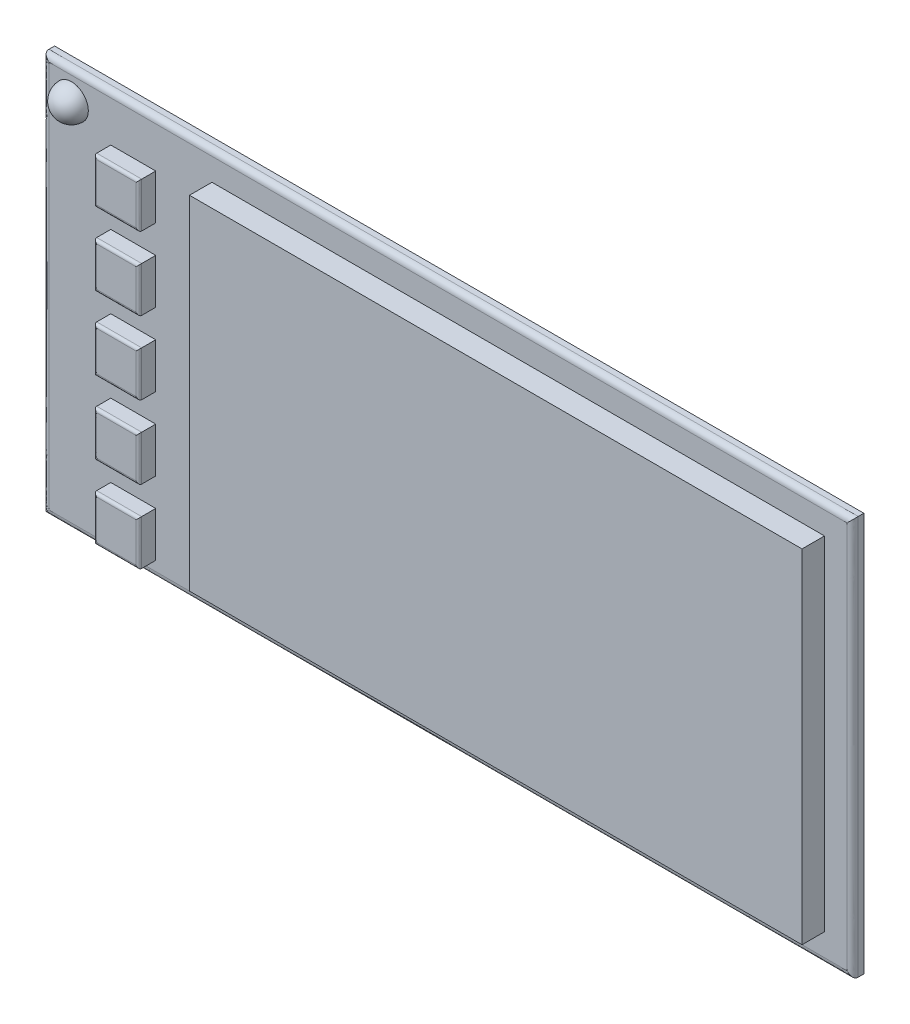
SolidWorks part; units mm, degrees
ref_plane "Front Plane" through (0, 0, 0) normal (0, 0, 1) x (1, 0, 0)
ref_plane "Top Plane" through (0, 0, 0) normal (0, 1, 0) x (1, 0, 0)
ref_plane "Right Plane" through (0, 0, 0) normal (1, 0, 0) x (0, 0, -1)
sketch "Sketch1" plane through (0, 0, 0) normal (0, 0, 1) x (1, 0, 0)
  line L0 (-42, 30.5) -> (-42, -30.5)
  line L1 (-72, 35.5) -> (72, 35.5)
  line L2 (-72, 35.5) -> (-72, -35.5)
  line L3 (-72, -35.5) -> (72, -35.5)
  line L4 (72, 35.5) -> (72, -35.5)
  line L5 (-72, 35.5) -> (72, -35.5) construction
  line L6 (-72, -35.5) -> (72, 35.5) construction
  line L7 (-42, -30.5) -> (67, -30.5)
  line L8 (67, 30.5) -> (67, -30.5)
  line L9 (-52, 14.2363) -> (-52, 6.2363)
  line L10 (-42, 30.5) -> (67, 30.5)
  line L11 (-42, 35.5) -> (-42, -35.5) construction
  line L12 (-72, 30.5) -> (67, 30.5) construction
  line L13 (-72, -30.5) -> (67, -30.5) construction
  line L14 (-52, 27.2363) -> (-60, 27.2363)
  line L15 (-52, 27.2363) -> (-52, 19.2363)
  line L16 (-52, 19.2363) -> (-60, 19.2363)
  line L17 (-60, 27.2363) -> (-60, 19.2363)
  line L18 (-52, 27.2363) -> (-60, 19.2363) construction
  line L19 (-52, 19.2363) -> (-60, 27.2363) construction
  line L20 (-52, 14.2363) -> (-60, 14.2363)
  line L21 (-60, 14.2363) -> (-60, 6.2363)
  line L22 (-52, 6.2363) -> (-60, 6.2363)
  line L23 (-52, 1.2363) -> (-52, -6.7637)
  line L24 (-52, 1.2363) -> (-60, 1.2363)
  line L25 (-60, 1.2363) -> (-60, -6.7637)
  line L26 (-52, -6.7637) -> (-60, -6.7637)
  line L27 (-52, -11.7637) -> (-52, -19.7637)
  line L28 (-52, -11.7637) -> (-60, -11.7637)
  line L29 (-60, -11.7637) -> (-60, -19.7637)
  line L30 (-52, -19.7637) -> (-60, -19.7637)
  line L31 (-52, -24.7637) -> (-52, -32.7637)
  line L32 (-52, -24.7637) -> (-60, -24.7637)
  line L33 (-60, -24.7637) -> (-60, -32.7637)
  line L34 (-52, -32.7637) -> (-60, -32.7637)
  circle A0 centre (-67, 30.5) radius 2.5
  point P0 (0, 0)
  point P12 (-56, 23.2363)
  dimension "D7" = 5
  dimension "D1" = 144
  dimension "D2" = 71
  dimension "D5" = 109
  dimension "D6" = 109
  dimension "D8" = 5
  dimension "D9" = 5
  dimension "D10" = 8
  dimension "D11" = 12
  dimension "D12" = 8.2637
  dimension "D14" = 5
  dimension "D15" = 12
  dimension "D3" = 30
  dimension "D4" = 5
  dimension "D13" = 5
extrude "Boss-Extrude1" add sketch "Sketch1" along normal blind 2
extrude "Boss-Extrude2" add sketch "Sketch1<2>" along normal blind 6 contours L10 L0 L7 L8 region at (12.5, 0, 0)
sketch "Sketch1<2>" plane through (0, 0, 0) normal (0, 0, 1) x (1, 0, 0) same geometry as "Sketch1"
extrude "Boss-Extrude3" add sketch "Sketch1<3>" along normal blind 5 contours L22 L9 L20 L21 | L26 L23 L24 L25 | L30 L27 L28 L29 | L34 L31 L32 L33 | L16 L17 L14 L15 region at (-56, 10.2363, 0) region at (-56, -2.7637, 0) region at (-56, -15.7637, 0) region at (-56, -28.7637, 0)
sketch "Sketch1<3>" plane through (0, 0, 0) normal (0, 0, 1) x (1, 0, 0) same geometry as "Sketch1"
sketch "Sketch3" plane through (0, 0, 2) normal (0, 0, 1) x (1, 0, 0)
  circle A0 centre (-67, 30.5) radius 3
  dimension "D1" = 6
extrude "Boss-Extrude4" add sketch "Sketch3" along normal blind 3
fillet "Fillet3" radius 3 1 edges at (-64, 30.5, 5)
fillet "Fillet4" radius 0.5 20 edges at (-60, -28.7637, 5) (-56, -24.7637, 5) (-52, -28.7637, 5) (-56, -32.7637, 5) (-60, -15.7637, 5) (-56, -11.7637, 5) (-52, -15.7637, 5) (-56, -19.7637, 5) (-60, -2.7637, 5) (-56, 1.2363, 5) (-52, -2.7637, 5) (-56, -6.7637, 5) (-60, 10.2363, 5) (-56, 14.2363, 5) (-52, 10.2363, 5) (-56, 6.2363, 5) (-56, 19.2363, 5) (-60, 23.2363, 5) (-56, 27.2363, 5) (-52, 23.2363, 5) conic rho 0.5
fillet "Fillet5" radius 1 4 edges at (72, 0, 2) (0, -35.5, 2) (-72, 0, 2) (0, 35.5, 2) conic rho 0.5
